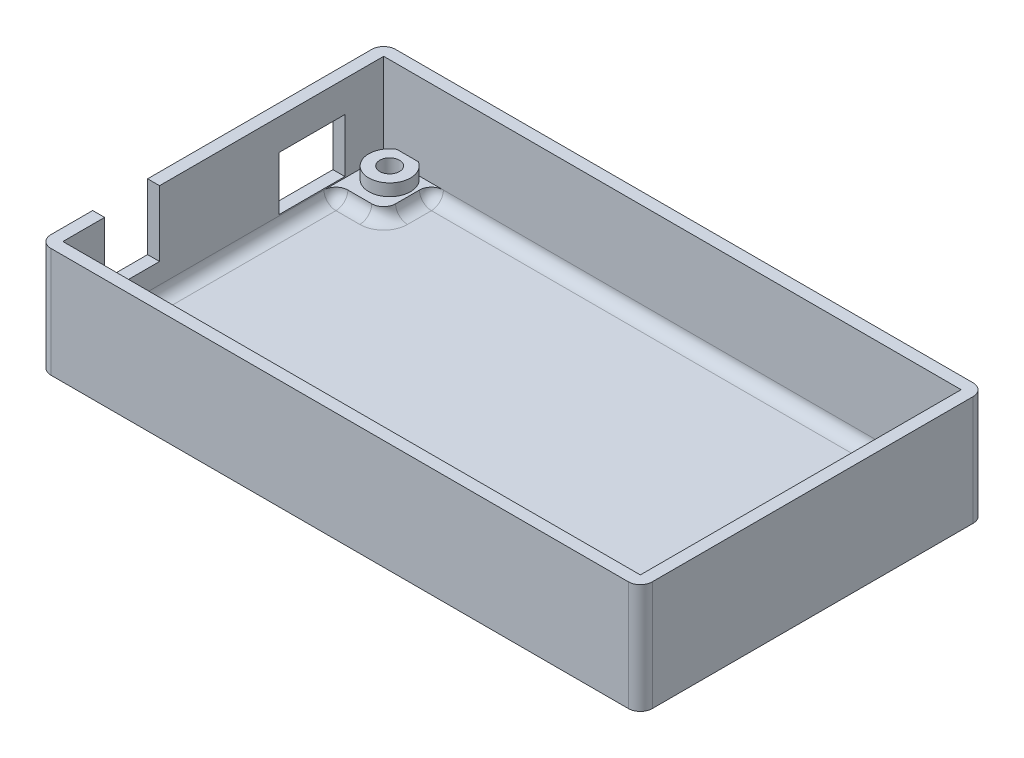
SolidWorks part; units mm, degrees
other "Markup1"
sketch "Sketch7" plane through (-50.25, 18.4, 29) normal (-0.4215, 0.901, 0.1023) x (0.0084, -0.1089, 0.994)
ref_plane "Front Plane" through (0, 0, 0) normal (0, 0, 1) x (1, 0, 0)
ref_plane "Top Plane" through (0, 0, 0) normal (0, 1, 0) x (1, 0, 0)
ref_plane "Right Plane" through (0, 0, 0) normal (1, 0, 0) x (0, 0, -1)
sketch "Sketch1" plane through (0, 0, 0) normal (0, 1, 0) x (1, 0, 0)
  line L1 (-48.25, -27) -> (48.5, -27)
  line L2 (-48.25, -27) -> (-48.25, 26.75)
  line L3 (-48.25, 26.75) -> (48.5, 26.75)
  line L4 (48.5, -27) -> (48.5, 26.75)
  line L5 (-50.25, 28.75) -> (50.5, 28.75)
  line L6 (-50.25, 28.75) -> (-50.25, -29)
  line L7 (-50.25, -29) -> (50.5, -29)
  line L8 (50.5, 28.75) -> (50.5, -29)
  circle A0 centre (44.5, -14.25) radius 1.65
  circle A1 centre (44.5, 14) radius 1.65
  circle A2 centre (-44.25, 23.75) radius 1.65
  circle A3 centre (-44.25, -24) radius 1.65
  dimension "D5" = 3.3
  dimension "D6" = 12.75
  dimension "D1" = 26.75
  dimension "D2" = 53.75
  dimension "D3" = 96.75
  dimension "D4" = 48.25
  dimension "D7" = 12.75
  dimension "D8" = 4
  dimension "D9" = 4
  dimension "D10" = 4
  dimension "D11" = 4
  dimension "D12" = 3
  dimension "D13" = 3
  dimension "D14" = 2
  dimension "D15" = 2
  dimension "D16" = 2
  dimension "D17" = 2
extrude "Boss-Extrude1" add sketch "Sketch1" along normal blind 2 contours L1 L4 L3 L2 A3 A2 A1 A0 | L8 L5 L6 L7 L4 L1 L2 L3 region at (0.125, 0, 0.125) region at (0.125, 0, -27.5887)
sketch "Sketch2" plane through (0, 2, 0) normal (0, 1, 0) x (1, 0, 0)
  line L0 (-44.3034, -20.5004) -> (-40.7879, -23.4862)
  line L5 (-46.0528, 26.75) -> (-42.4472, 26.75)
  line L7 (-46.0528, -27) -> (-42.4472, -27)
  circle A0 centre (44.5, 14) radius 3.5
  circle A1 centre (44.5, -14.25) radius 3.5
  arc A2 (-42.4472, -27) -> (-40.7879, -23.4862) centre (-44.25, -24) ccw
  arc A3 (-46.0528, 26.75) -> (-42.4472, 26.75) centre (-44.25, 23.75) ccw
  circle A4 centre (44.5, 14) radius 1.65
  circle A5 centre (44.5, -14.25) radius 1.65
  circle A6 centre (-44.25, -24) radius 1.65
  circle A7 centre (-44.25, 23.75) radius 1.65
  circle A8 centre (44.5, 14) radius 1.65 construction
  circle A9 centre (44.5, -14.25) radius 1.65 construction
  circle A10 centre (-44.25, 23.75) radius 1.65 construction
  circle A11 centre (-44.25, -24) radius 1.65 construction
  arc A12 (-44.3034, -20.5004) -> (-46.0528, -27) centre (-44.25, -24) ccw
  dimension "D1" = 7
extrude "Boss-Extrude2" add sketch "Sketch2" along normal blind 4
sketch "Sketch3" plane through (0, 2, 0) normal (0, 1, 0) x (1, 0, 0)
  line L1 (-50.25, 28.75) -> (50.5, 28.75)
  line L2 (-50.25, 28.75) -> (-50.25, -29)
  line L3 (-50.25, -29) -> (50.5, -29)
  line L4 (50.5, 28.75) -> (50.5, -29)
  line L5 (-48.25, 26.75) -> (48.5, 26.75)
  line L6 (-48.25, 26.75) -> (-48.25, -27)
  line L7 (-48.25, -27) -> (48.5, -27)
  line L8 (48.5, 26.75) -> (48.5, -27)
  dimension "D1" = 2
  dimension "D2" = 2
  dimension "D3" = 2
  dimension "D4" = 2
extrude "Boss-Extrude3" add sketch "Sketch3" along normal blind 16.4
fillet "Fillet1" radius 2 4 edges at (50.5, 9.2, 29) (50.5, 9.2, -28.75) (-50.25, 9.2, 29) (-50.25, 9.2, -28.75)
sketch "Sketch5" plane through (0, 2, 0) normal (0, 1, 0) x (1, 0, 0)
  line L0 (48.5, -27) -> (48.5, 26.75) construction
  line L1 (40.5, 18) -> (48.5, 18)
  line L2 (40.5, 18) -> (40.5, 10)
  line L3 (40.5, 10) -> (48.5, 10)
  line L4 (48.5, 18) -> (48.5, 10)
  line L5 (40.5, -10.25) -> (48.5, -10.25)
  line L6 (40.5, -10.25) -> (40.5, -18.25)
  line L7 (40.5, -18.25) -> (48.5, -18.25)
  line L8 (48.5, -10.25) -> (48.5, -18.25)
  line L9 (-48.25, -19) -> (-40.25, -19)
  line L10 (-48.25, -19) -> (-48.25, -27)
  line L11 (-48.25, -27) -> (-40.25, -27)
  line L12 (-40.25, -19) -> (-40.25, -27)
  line L13 (-48.25, 26.75) -> (-40.25, 26.75)
  line L14 (-48.25, 26.75) -> (-48.25, 18.75)
  line L15 (-48.25, 18.75) -> (-40.25, 18.75)
  line L16 (-40.25, 26.75) -> (-40.25, 18.75)
  circle A0 centre (44.5, 14) radius 1.65 construction
  circle A1 centre (44.5, -14.25) radius 1.65 construction
  circle A2 centre (-44.25, 23.75) radius 1.65
  circle A3 centre (-44.25, -24) radius 1.65
  circle A4 centre (44.5, 14) radius 1.65
  circle A5 centre (44.5, -14.25) radius 1.65
  circle A6 centre (-44.25, -24) radius 1.65 construction
  circle A7 centre (-44.25, 23.75) radius 1.65 construction
  dimension "D1" = 8
  dimension "D2" = 8
  dimension "D3" = 4
  dimension "D4" = 8
  dimension "D5" = 8
  dimension "D6" = 4
  dimension "D7" = 8
  dimension "D8" = 8
  dimension "D9" = 8
  dimension "D10" = 8
extrude "Boss-Extrude4" add sketch "Sketch5" along normal blind 2
fillet "Fillet3" radius 2 14 edges at (-48.25, 3, 19) (-40.25, 3, 19) (-40.25, 3, 27) (-48.25, 3, -18.75) (-40.25, 3, -18.75) (-40.25, 3, -26.75) (48.5, 3, 18.25) (40.5, 3, 18.25) (48.5, 3, 10.25) (48.5, 3, -18) (40.5, 3, 10.25) (48.5, 3, -10) (40.5, 3, -18) (40.5, 3, -10)
fillet "Fillet4" radius 2 30 edges at (48.5, 2, -23.375) (47.9142, 2, -18.5858) (44.5, 2, -18) (41.0858, 2, -17.4142) (48.5, 2, 23.625) (47.9142, 2, 18.8358) (44.5, 2, 18.25) (41.0858, 2, 17.6642) (40.5, 2, 14.25) (41.0858, 2, 10.8358) (44.5, 2, 10.25) (47.9142, 2, 9.6642) (48.5, 2, 0.125) (47.9142, 2, -9.4142) (44.5, 2, -10) (41.0858, 2, -10.5858) (5.125, 2, 27) (-39.6642, 2, 26.4142) (-40.25, 2, 23) (-40.8358, 2, 19.5858) (5.125, 2, -26.75) (-39.6642, 2, -26.1642) (-40.25, 2, -22.75) (-40.8358, 2, -19.3358) (-44.25, 2, -18.75) (-47.6642, 2, -18.1642) (-48.25, 2, 0.125) (-47.6642, 2, 18.4142) (40.5, 2, -14) (-44.25, 2, 19)
sketch "Sketch4" plane through (0, 0, 0) normal (0, -1, 0) x (1, 0, 0)
  line L1 (40.5, -11.6906) -> (40.5, -16.3094)
  line L2 (40.5, -16.3094) -> (44.5, -18.6188)
  line L3 (44.5, -18.6188) -> (48.5, -16.3094)
  line L4 (48.5, -16.3094) -> (48.5, -11.6906)
  line L5 (48.5, -11.6906) -> (44.5, -9.3812)
  line L6 (44.5, -9.3812) -> (40.5, -11.6906)
  line L7 (40.355, 11.8869) -> (44.355, 9.5775)
  line L8 (44.355, 9.5775) -> (48.355, 11.8869)
  line L9 (48.355, 11.8869) -> (48.355, 16.5057)
  line L10 (48.355, 16.5057) -> (44.355, 18.8151)
  line L11 (44.355, 18.8151) -> (40.355, 16.5057)
  line L12 (40.355, 16.5057) -> (40.355, 11.8869)
  line L13 (-48.25, 26.3094) -> (-48.25, 21.6906)
  line L14 (-48.25, 21.6906) -> (-44.25, 19.3812)
  line L15 (-44.25, 19.3812) -> (-40.25, 21.6906)
  line L16 (-40.25, 21.6906) -> (-40.25, 26.3094)
  line L17 (-40.25, 26.3094) -> (-44.25, 28.6188)
  line L18 (-44.25, 28.6188) -> (-48.25, 26.3094)
  line L19 (-44.25, -19.1312) -> (-48.25, -21.4406)
  line L20 (-48.25, -21.4406) -> (-48.25, -26.0594)
  line L21 (-48.25, -26.0594) -> (-44.25, -28.3688)
  line L22 (-44.25, -28.3688) -> (-40.25, -26.0594)
  line L23 (-40.25, -26.0594) -> (-40.25, -21.4406)
  line L24 (-40.25, -21.4406) -> (-44.25, -19.1312)
  circle A5 centre (44.5, -14) radius 1.65 construction
  circle A6 centre (-44.25, -23.75) radius 1.65 construction
  circle A7 centre (-44.25, 24) radius 1.65 construction
  circle A8 centre (44.5, -14) radius 4 construction
  circle A9 centre (44.355, 14.1963) radius 4 construction
  circle A10 centre (-44.25, 24) radius 4 construction
  circle A11 centre (-44.25, -23.75) radius 4 construction
  dimension "D2" = 8
  dimension "D3" = 8
  dimension "D4" = 8
  dimension "D5" = 8
sketch "Sketch6" plane through (-50.25, 0, 0) normal (-1, 0, 0) x (0, 0, 1)
  line L0 (-28.75, 0) -> (-28.75, 18.4) construction
  line L1 (-26.75, 18.4) -> (27, 18.4)
  line L2 (-26.75, 18.4) -> (-26.75, 7.4)
  line L3 (-26.75, 7.4) -> (27, 7.4)
  line L4 (27, 18.4) -> (27, 7.4)
  line L5 (-26.75, 0) -> (27, 0) construction
  line L6 (29, 18.4) -> (29, 0) construction
  line L7 (-26.75, 18.4) -> (27, 18.4) construction
  line L9 (-20.25, 13.2) -> (-9.25, 13.2)
  line L10 (-20.25, 13.2) -> (-20.25, 4.2)
  line L11 (-20.25, 4.2) -> (-9.25, 4.2)
  line L12 (-9.25, 13.2) -> (-9.25, 4.2)
  line L13 (-18.75, 10) -> (-10.75, 10)
  line L14 (-18.75, 10) -> (-18.75, 7.4)
  line L15 (-18.75, 7.4) -> (-10.75, 7.4)
  line L16 (-10.75, 10) -> (-10.75, 7.4)
  line L17 (10.8, 18.4) -> (20, 18.4)
  line L18 (10.8, 18.4) -> (10.8, 7.4)
  line L19 (10.8, 7.4) -> (20, 7.4)
  line L20 (20, 18.4) -> (20, 7.4)
  point P20 (-14.75, 10)
  point P21 (-18.75, 8.7)
  dimension "D1" = 2
  dimension "D2" = 7.4
  dimension "D3" = 2
  dimension "D4" = 0
  dimension "D5" = 11
  dimension "D6" = 9
  dimension "D7" = 2.6
  dimension "D8" = 8
  dimension "D9" = 0
  dimension "D10" = 8
  dimension "D11" = 5.5
  dimension "D12" = 4.5
  dimension "D13" = 7
  dimension "D14" = 11
  dimension "D15" = 0
  dimension "D16" = 9.2
extrude "Cut-Extrude2" cut sketch "Sketch6" against normal blind 2 contours L20 L1 L18 L3 | L12 L3 L10 L11 | L13 L16 L3 L12 L9 L10 L14 | L16 L13 L14 L3 region at (-50.25, 12.9, 15.4) region at (-50.25, 11.074, -14.75) region at (-50.25, 5.8, -14.75) region at (-50.25, 8.7, -14.75)
extrude "Cut-Extrude3" cut sketch "Sketch4" against normal blind 2
